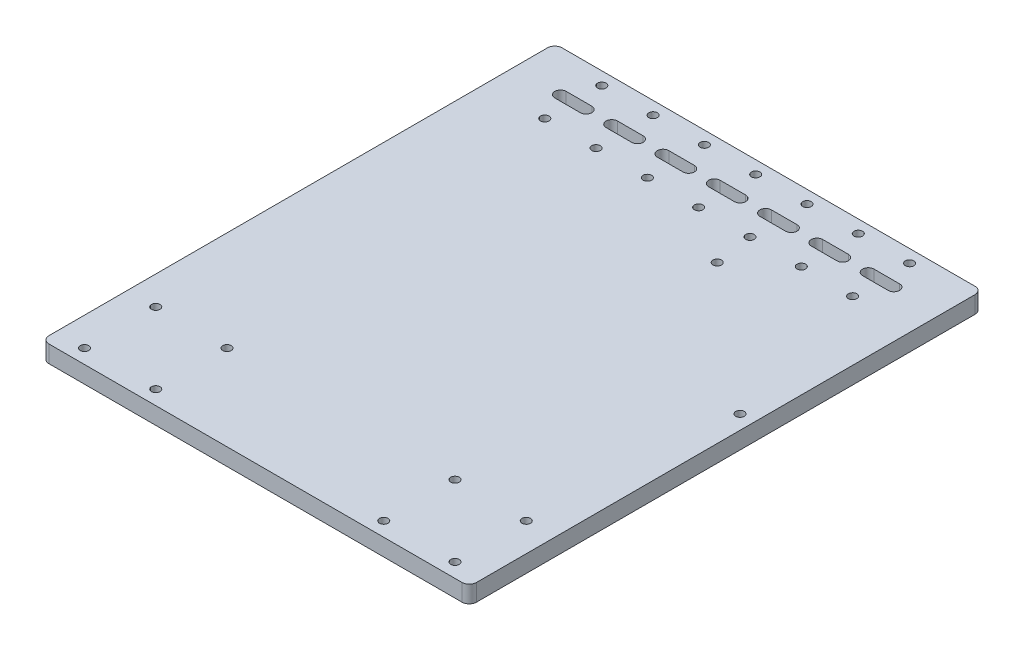
SolidWorks part; units mm, degrees
ref_plane "Front Plane" through (0, 0, 0) normal (0, 0, 1) x (1, 0, 0)
ref_plane "Top Plane" through (0, 0, 0) normal (0, 1, 0) x (1, 0, 0)
ref_plane "Right Plane" through (0, 0, 0) normal (1, 0, 0) x (0, 0, -1)
sketch "Sketch1" plane through (0, 0, 0) normal (0, 1, 0) x (1, 0, 0)
  line L0 (75, 180) -> (75, 0) construction
  line L1 (2.54, 0) -> (147.46, 0)
  line L2 (0, 2.54) -> (0, 177.46)
  line L3 (2.54, 180) -> (147.46, 180)
  line L4 (150, 2.54) -> (150, 177.46)
  line L5 (133.5, 165.5) -> (124.5, 165.5) construction
  line L7 (133.5, 167.5) -> (124.5, 167.5)
  line L8 (16.5, 165.5) -> (25.5, 165.5) construction
  line L9 (16.5, 167.5) -> (25.5, 167.5)
  line L10 (16.5, 163.5) -> (25.5, 163.5)
  line L11 (34.5, 165.5) -> (43.5, 165.5) construction
  line L12 (34.5, 167.5) -> (43.5, 167.5)
  line L13 (34.5, 163.5) -> (43.5, 163.5)
  line L14 (52.5, 165.5) -> (61.5, 165.5) construction
  line L15 (52.5, 167.5) -> (61.5, 167.5)
  line L16 (52.5, 163.5) -> (61.5, 163.5)
  line L17 (70.5, 165.5) -> (79.5, 165.5) construction
  line L18 (70.5, 167.5) -> (79.5, 167.5)
  line L19 (70.5, 163.5) -> (79.5, 163.5)
  line L20 (133.5, 163.5) -> (124.5, 163.5)
  line L21 (115.5, 165.5) -> (106.5, 165.5) construction
  line L22 (115.5, 167.5) -> (106.5, 167.5)
  line L23 (115.5, 163.5) -> (106.5, 163.5)
  line L24 (97.5, 165.5) -> (88.5, 165.5) construction
  line L25 (97.5, 167.5) -> (88.5, 167.5)
  line L26 (97.5, 163.5) -> (88.5, 163.5)
  arc A0 (150, 177.46) -> (147.46, 180) centre (147.46, 177.46) ccw
  arc A1 (147.46, 0) -> (150, 2.54) centre (147.46, 2.54) ccw
  arc A2 (2.54, 0) -> (0, 2.54) centre (2.54, 2.54) cw
  arc A3 (2.54, 180) -> (0, 177.46) centre (2.54, 177.46) ccw
  circle A4 centre (10, 30) radius 1.5
  circle A5 centre (35, 30) radius 1.5
  circle A6 centre (35, 5) radius 1.5
  circle A7 centre (10, 5) radius 1.5
  circle A8 centre (140, 5) radius 1.5
  circle A9 centre (115, 5) radius 1.5
  circle A10 centre (115, 30) radius 1.5
  circle A11 centre (140, 30) radius 1.5
  circle A12 centre (75, 155.5) radius 1.5
  circle A13 centre (39, 155.5) radius 1.5
  circle A14 centre (21, 155.5) radius 1.5
  circle A15 centre (57, 155.5) radius 1.5
  circle A16 centre (93, 155.5) radius 1.5
  circle A17 centre (111, 155.5) radius 1.5
  circle A18 centre (129, 155.5) radius 1.5
  circle A26 centre (129, 175.5) radius 1.5
  circle A27 centre (111, 175.5) radius 1.5
  circle A28 centre (93, 175.5) radius 1.5
  circle A29 centre (75, 175.5) radius 1.5
  circle A30 centre (57, 175.5) radius 1.5
  circle A31 centre (39, 175.5) radius 1.5
  circle A32 centre (21, 175.5) radius 1.5
  circle A51 centre (145, 100) radius 1.5
  circle A52 centre (95, 142) radius 1.5
  arc A53 (16.5, 167.5) -> (16.5, 163.5) centre (16.5, 165.5) ccw
  arc A54 (25.5, 163.5) -> (25.5, 167.5) centre (25.5, 165.5) ccw
  arc A55 (34.5, 167.5) -> (34.5, 163.5) centre (34.5, 165.5) ccw
  arc A56 (43.5, 163.5) -> (43.5, 167.5) centre (43.5, 165.5) ccw
  arc A57 (52.5, 167.5) -> (52.5, 163.5) centre (52.5, 165.5) ccw
  arc A58 (61.5, 163.5) -> (61.5, 167.5) centre (61.5, 165.5) ccw
  arc A59 (70.5, 167.5) -> (70.5, 163.5) centre (70.5, 165.5) ccw
  arc A60 (79.5, 163.5) -> (79.5, 167.5) centre (79.5, 165.5) ccw
  arc A61 (133.5, 167.5) -> (133.5, 163.5) centre (133.5, 165.5) cw
  arc A62 (124.5, 163.5) -> (124.5, 167.5) centre (124.5, 165.5) cw
  arc A63 (115.5, 167.5) -> (115.5, 163.5) centre (115.5, 165.5) cw
  arc A64 (106.5, 163.5) -> (106.5, 167.5) centre (106.5, 165.5) cw
  arc A65 (97.5, 167.5) -> (97.5, 163.5) centre (97.5, 165.5) cw
  arc A66 (88.5, 163.5) -> (88.5, 167.5) centre (88.5, 165.5) cw
  point P11 (0, 0)
  point P50 (21, 165.5)
  point P56 (39, 165.5)
  point P81 (57, 165.5)
  point P88 (75, 165.5)
  point P101 (129, 165.5)
  point P108 (111, 165.5)
  point P123 (93, 165.5)
  dimension "D1" = 2.54
  dimension "D4" = 3
  dimension "D9" = 3
  dimension "D10" = 18
  dimension "D11" = 18
  dimension "D12" = 18
  dimension "D13" = 9
  dimension "D18" = 180
  dimension "D19" = 100
  dimension "D22" = 5
  dimension "D23" = 3
  dimension "D25" = 3
  dimension "D26" = 50
  dimension "D27" = 42
  dimension "D30" = 3
  dimension "D15" = 10
  dimension "D3" = 150
  dimension "D5" = 25
  dimension "D6" = 25
  dimension "D7" = 10
  dimension "D8" = 5
  dimension "D14" = 10
  dimension "D16" = 4.5
  dimension "D17" = 4
extrude "Boss-Extrude1" add sketch "Sketch1" along normal blind 6
